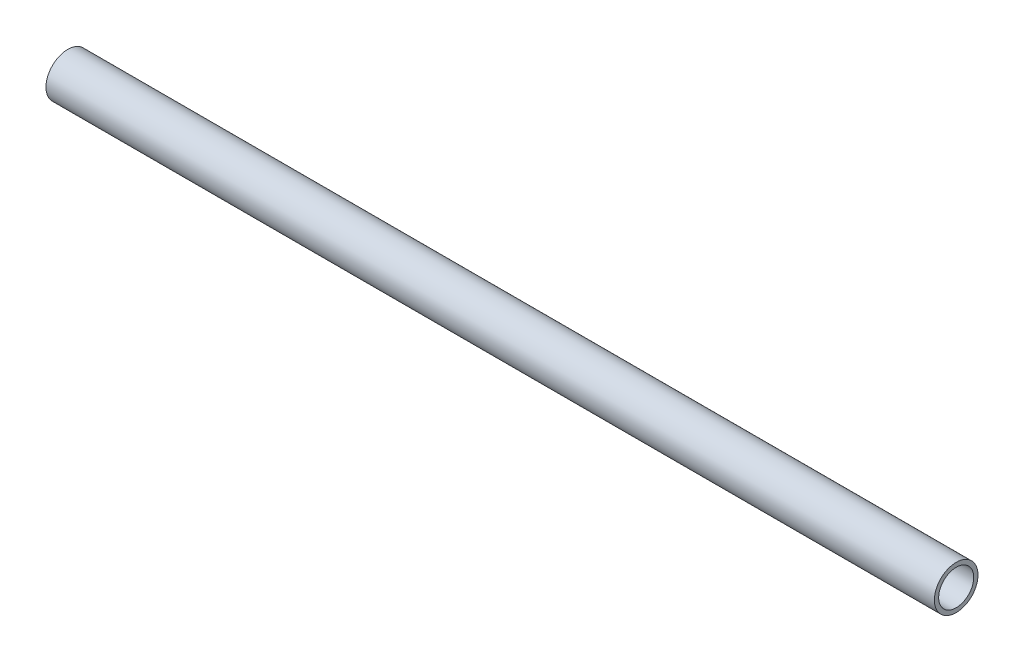
SolidWorks part; units mm, degrees
ref_plane "Vorne" through (0, 0, 0) normal (0, 0, 1) x (1, 0, 0)
ref_plane "Oben" through (0, 0, 0) normal (0, 1, 0) x (1, 0, 0)
ref_plane "Seite" through (0, 0, 0) normal (1, 0, 0) x (0, 0, -1)
sketch "Skizze1" plane through (0, 0, 0) normal (1, 0, 0) x (0, 0, -1)
  circle A0 centre (0, 0) radius 2.55
  circle A1 centre (0, 0) radius 2.05
  dimension "D1" = 4.1
  dimension "D2" = 5.1
extrude "Aufsatz-Linear austragen1" add sketch "Skizze1" along normal mid plane 103.9
